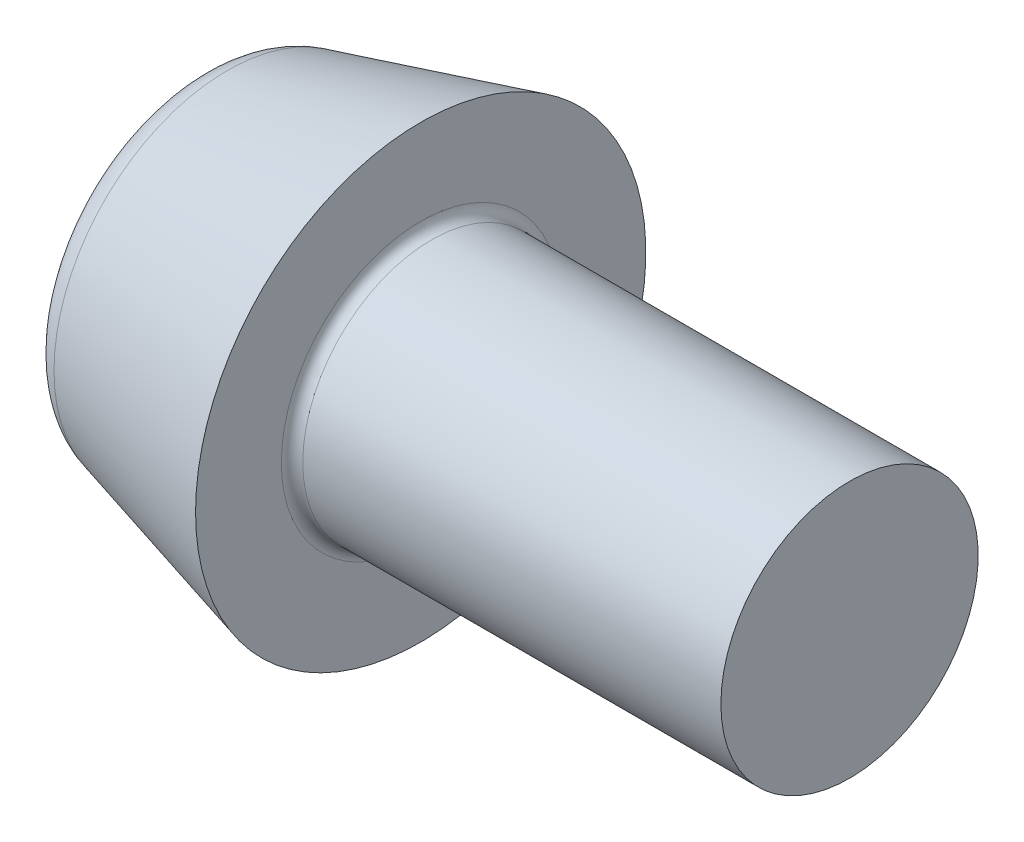
SolidWorks part; units mm, degrees
ref_plane "Front" through (0, 0, 0) normal (0, 0, 1) x (1, 0, 0)
ref_plane "Top" through (0, 0, 0) normal (0, 1, 0) x (1, 0, 0)
ref_plane "Right" through (0, 0, 0) normal (1, 0, 0) x (0, 0, -1)
sketch "Sketch1" plane through (0, 0, 0) normal (0, 0, 1) x (1, 0, 0)
  line L0 (0, 0) -> (30.5, 0)
  line L1 (30.5, 0) -> (30.5, 6)
  line L2 (30.5, 6) -> (10.5, 6)
  line L3 (10.5, 6) -> (10.5, 10.5)
  line L4 (10.5, 10.5) -> (0, 7.6865)
  line L5 (0, 7.6865) -> (0, 0)
  line L6 (-26.4886, 0) -> (67.8543, 0) construction
  line L7 (-6.0327, 10.5) -> (19.105, 10.5) construction
  dimension "D1" = 15
  dimension "L" = 20
  dimension "d" = 12
  dimension "K" = 10.5
  dimension "dk" = 21
revolve "Base-Revolve" add sketch "Sketch1" angle 360 about L6
fillet "Fillet1" radius 0.5 1 edges at (10.5, 0, 6)
fillet "Fillet2" radius 2 1 edges at (0, 0, 7.6865)
